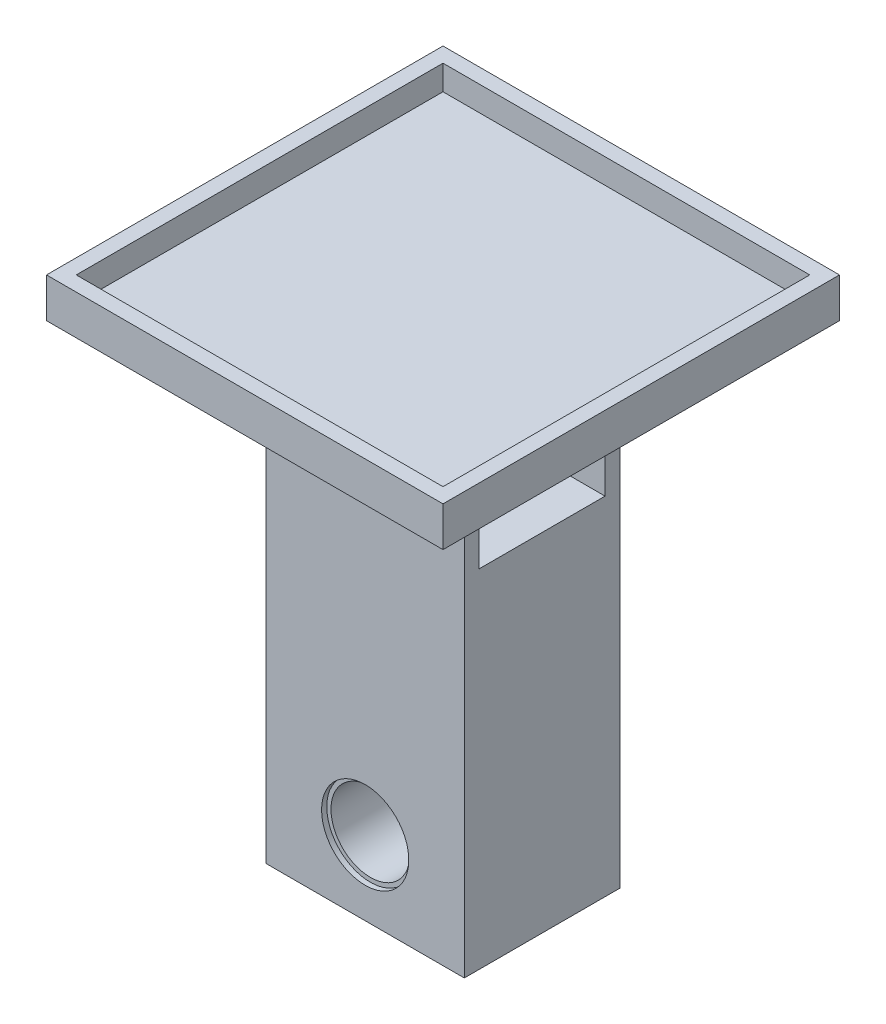
SolidWorks part; units mm, degrees
material "Custom Plastic"
ref_plane "Front Plane" through (0, 0, 0) normal (0, 0, 1) x (1, 0, 0)
ref_plane "Top Plane" through (0, 0, 0) normal (0, 1, 0) x (1, 0, 0)
ref_plane "Right Plane" through (0, 0, 0) normal (1, 0, 0) x (0, 0, -1)
sketch "Sketch2" plane through (0, 0, 0) normal (0, 0, 1) x (1, 0, 0)
  circle A0 centre (0, 0) radius 7.5
  dimension "D1" = 15
extrude "Boss-Extrude1" add sketch "Sketch2" along normal mid plane 5
sketch "Sketch3" plane through (0, 0, 0) normal (1, 0, 0) x (0, 0, -1)
  line L0 (-15.7, 44.5) -> (-12.7, 44.5)
  line L1 (-12.7, 44.5) -> (-12.7, 17.5)
  line L2 (-12.7, 17.5) -> (12.7, 17.5)
  line L3 (-15.7, 44.5) -> (-15.7, 7.5)
  line L5 (0, 40.7714) -> (0, -28.5595) construction
  line L6 (15.7, 44.5) -> (15.7, 7.5)
  line L7 (12.7, 44.5) -> (12.7, 17.5)
  line L8 (15.7, 44.5) -> (12.7, 44.5)
  line L10 (-15.7, 7.5) -> (-15.7, -52.5)
  line L12 (-15.7, -52.5) -> (15.7, -52.5)
  line L13 (15.7, -52.5) -> (15.7, 7.5)
  line L14 (-2.5, -7.5) -> (2.5, -7.5) construction
  line L15 (2.5, 7.5) -> (-2.5, 7.5) construction
  dimension "D1" = 27
  dimension "D2" = 3
  dimension "D3" = 45
  dimension "D4" = 12.7
  dimension "D5" = 10
extrude "Boss-Extrude3" add sketch "Sketch3" along normal mid plane 40 contours L5 L2 L1 L0 L3 | L5 L10 L12 | L5 L12 L13 | L2 L5 L6 L8 L7 region at (0, -14.1708, 0)
sketch "Sketch4" plane through (0, 0, 15.7) normal (0, 0, 1) x (1, 0, 0)
  line L0 (0, -89.3007) -> (0, 55.521) construction
  line L1 (20, 17.5) -> (-20, 17.5) construction
  circle A0 centre (0, 30.2) radius 3
  dimension "D1" = 6
  dimension "D2" = 12.7
extrude "Cut-Extrude1" cut sketch "Sketch4" against normal up to surface (31.4 mm away) up to face at (0, -4, -15.7)
sketch "Sketch5" plane through (0, 44.5, 0) normal (0, 1, 0) x (1, 0, 0)
  line L0 (40, 40) -> (-40, -40) construction
  line L1 (-40, 40) -> (40, 40)
  line L2 (-40, 40) -> (-40, -40)
  line L3 (-40, -40) -> (40, -40)
  line L4 (40, 40) -> (40, -40)
  point P4 (0, 0)
  dimension "D1" = 80
  dimension "D2" = 80
extrude "Boss-Extrude4" add sketch "Sketch5" along normal blind 3
sketch "Sketch6" plane through (0, 47.5, 0) normal (0, 1, 0) x (1, 0, 0)
  line L0 (37, 37) -> (-37, -37) construction
  line L1 (-37, -37) -> (37, -37)
  line L2 (-37, -37) -> (-37, 37)
  line L3 (-37, 37) -> (37, 37)
  line L4 (37, -37) -> (37, 37)
  line L6 (-40, -40) -> (40, -40)
  line L7 (-40, -40) -> (-40, 40)
  line L8 (-40, 40) -> (40, 40)
  line L9 (40, -40) -> (40, 40)
  line L10 (-40, -40) -> (40, 40) construction
  line L11 (-40, 40) -> (40, -40) construction
  point P4 (0, 0)
  point P6 (0, 0)
  dimension "D1" = 3
  dimension "D2" = 3
extrude "Boss-Extrude5" add sketch "Sketch6" along normal blind 5
sketch "Sketch7" plane through (-20, 0, 0) normal (-1, 0, 0) x (0, 0, 1)
  line L0 (15.7, -52.5) -> (-15.7, -52.5) construction
  line L1 (-10.7, -37.5) -> (10.7, -37.5)
  line L2 (-10.7, -37.5) -> (-10.7, -52.5)
  line L3 (-10.7, -52.5) -> (10.7, -52.5)
  line L4 (10.7, -37.5) -> (10.7, -52.5)
  line L5 (-10.7, -37.5) -> (10.7, -52.5) construction
  line L6 (-10.7, -52.5) -> (10.7, -37.5) construction
  line L7 (15.7, 44.5) -> (15.7, -52.5) construction
  point P0 (0, -45)
  point P10 (0, -45)
  dimension "D1" = 5
  dimension "D2" = 15
extrude "Cut-Extrude2" [suppressed] cut sketch "Sketch7" against normal through all
sketch "Sketch8" plane through (0, 0, -15.7) normal (0, 0, -1) x (-1, 0, 0)
  line L0 (-20, -52.5) -> (20, -52.5) construction
  circle A0 centre (0, -37.5) radius 7.95
  circle A1 centre (0, 30.2) radius 3 construction
  dimension "D1" = 15.9
  dimension "D2" = 15
extrude "Cut-Extrude3" cut sketch "Sketch8" against normal through all
sketch "Sketch9" plane through (0, 0, -15.7) normal (0, 0, -1) x (-1, 0, 0)
  circle A0 centre (0, -37.5) radius 8.8
  dimension "D1" = 17.6
extrude "Cut-Extrude4" cut sketch "Sketch9" against normal blind 1.05
mirror "Mirror1" about plane through (0, 0, 0) normal (0, 0, 1) of "Cut-Extrude4"
